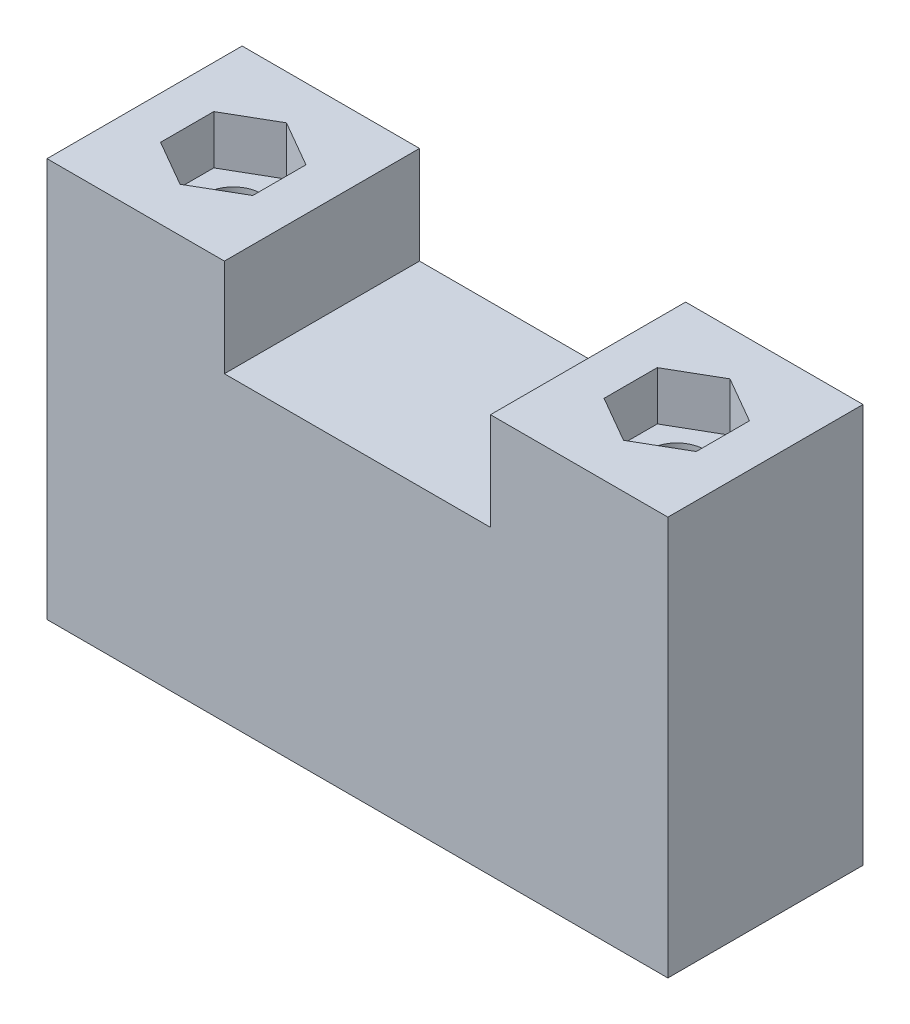
SolidWorks part; units mm, degrees
ref_plane "Front Plane" through (0, 0, 0) normal (0, 0, 1) x (1, 0, 0)
ref_plane "Top Plane" through (0, 0, 0) normal (0, 1, 0) x (1, 0, 0)
ref_plane "Right Plane" through (0, 0, 0) normal (1, 0, 0) x (0, 0, -1)
sketch "Sketch1" plane through (0, 0, 0) normal (0, 1, 0) x (1, 0, 0)
  line L1 (0, 0) -> (70, 0)
  line L2 (0, 0) -> (0, 22)
  line L3 (0, 22) -> (70, 22)
  line L4 (70, 0) -> (70, 22)
  line L7 (30.2143, -18.8036) -> (29.5714, -18.8036)
  dimension "D1" = 70
  dimension "D2" = 22
extrude "Boss-Extrude1" add sketch "Sketch1" along normal blind 45 contours L1 L4 L3 L2 region at (35, 0, -11)
sketch "Sketch2" plane through (0, 45, 0) normal (0, 1, 0) x (1, 0, 0)
  line L0 (0, 0) -> (70, 0) construction
  line L1 (20, 22) -> (50, 22)
  line L2 (20, 22) -> (20, 0)
  line L3 (20, 0) -> (50, 0)
  line L4 (50, 22) -> (50, 0)
  line L5 (20, 22) -> (50, 0) construction
  line L6 (20, 0) -> (50, 22) construction
  line L7 (35, 0) -> (35, 11) construction
  point P0 (35, 11)
  dimension "D1" = 30
  dimension "D2" = 22
extrude "Cut-Extrude1" cut sketch "Sketch2" against normal blind 11
sketch "Sketch3" plane through (0, 45, 0) normal (0, 1, 0) x (1, 0, 0)
  line L0 (35, 22) -> (35, 0) construction
  line L1 (50, 22) -> (20, 22) construction
  line L2 (20, 0) -> (50, 0) construction
  line L3 (20, 22) -> (20, 0) construction
  circle A0 centre (10, 11) radius 3.175
  circle A1 centre (60, 11) radius 3.175
  dimension "D1" = 6.35
  dimension "D2" = 10
extrude "Cut-Extrude2" cut sketch "Sketch3" against normal blind 69
sketch "Sketch4" plane through (0, 45, 0) normal (0, 1, 0) x (1, 0, 0)
  line L0 (35, 22) -> (35, 0) construction
  line L1 (10, 17) -> (4.8038, 14)
  line L2 (4.8038, 14) -> (4.8038, 8)
  line L3 (4.8038, 8) -> (10, 5)
  line L4 (10, 5) -> (15.1962, 8)
  line L5 (15.1962, 8) -> (15.1962, 14)
  line L6 (15.1962, 14) -> (10, 17)
  line L7 (50, 22) -> (20, 22) construction
  line L8 (20, 0) -> (50, 0) construction
  line L9 (54.8038, 14) -> (60, 17)
  line L10 (54.8038, 8) -> (54.8038, 14)
  line L11 (60, 5) -> (54.8038, 8)
  line L12 (65.1962, 8) -> (60, 5)
  line L13 (65.1962, 14) -> (65.1962, 8)
  line L14 (60, 17) -> (65.1962, 14)
  circle A0 centre (10, 11) radius 5.1962 construction
  circle A1 centre (60, 11) radius 5.1962 construction
  dimension "D1" = 6
extrude "Cut-Extrude3" cut sketch "Sketch4" against normal blind 5.5
